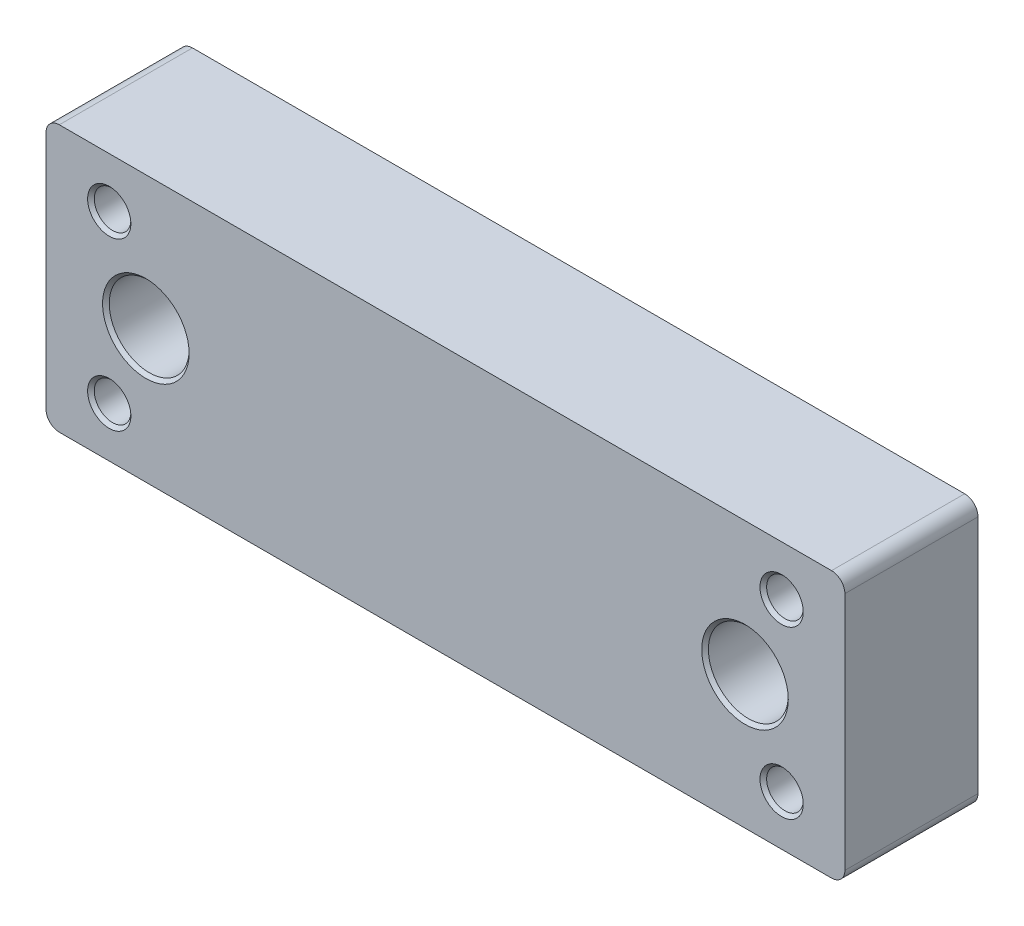
SolidWorks part; units mm, degrees
ref_plane "前视基准面" through (0, 0, 0) normal (0, 0, 1) x (1, 0, 0)
ref_plane "上视基准面" through (0, 0, 0) normal (0, 1, 0) x (1, 0, 0)
ref_plane "右视基准面" through (0, 0, 0) normal (1, 0, 0) x (0, 0, -1)
sketch "草图1" plane through (0, 0, 0) normal (0, 0, 1) x (1, 0, 0)
  line L1 (-60, 20) -> (60, 20)
  line L2 (-60, 20) -> (-60, -20)
  line L3 (-60, -20) -> (60, -20)
  line L4 (60, 20) -> (60, -20)
  dimension "D1" = 120
  dimension "D2" = 40
  dimension "D3" = 20
  dimension "D4" = 60
extrude "凸台-拉伸1" add sketch "草图1" along normal blind 20
sketch "草图2" plane through (0, 0, 20) normal (0, 0, 1) x (1, 0, 0)
  line L0 (0, 0) -> (0, 50000) construction
  line L2 (0, 0) -> (-50000, 0) construction
  circle A0 centre (45, 0) radius 6
  circle A1 centre (50.5, 12.5) radius 2.75
  circle A2 centre (50.5, -12.5) radius 2.75
  circle A3 centre (-50.5, -12.5) radius 2.75
  circle A4 centre (-50.5, 12.5) radius 2.75
  circle A5 centre (-45, 0) radius 6
  point P7 (-50.5, 9.1086)
  point P8 (50.5, -12.5)
  point P9 (0, 0)
  point P20 (50.5, -12.5)
  point P21 (50.5, -12.5)
  point P22 (51, -12.5)
  dimension "D1" = 45
  dimension "D4" = 5.5
  dimension "D5" = 12
  dimension "D6" = 12.5
  dimension "D2" = 50.5
  dimension "D3" = 12.5
extrude "切除-拉伸1" cut sketch "草图2" against normal blind 20
fillet "圆角1" radius 2 4 edges at (-60, 20, 10) (-60, -20, 10) (60, 20, 10) (60, -20, 10)
chamfer "倒角1" distance 0.5 angle 45 12 edges at (47.75, -12.5, 20) (47.75, -12.5, 0) (53.25, 12.5, 20) (53.25, 12.5, 0) (51, 0, 20) (51, 0, 0) (-47.75, -12.5, 20) (-47.75, -12.5, 0) (-53.25, 12.5, 20) (-53.25, 12.5, 0) (-51, 0, 20) (-51, 0, 0)
